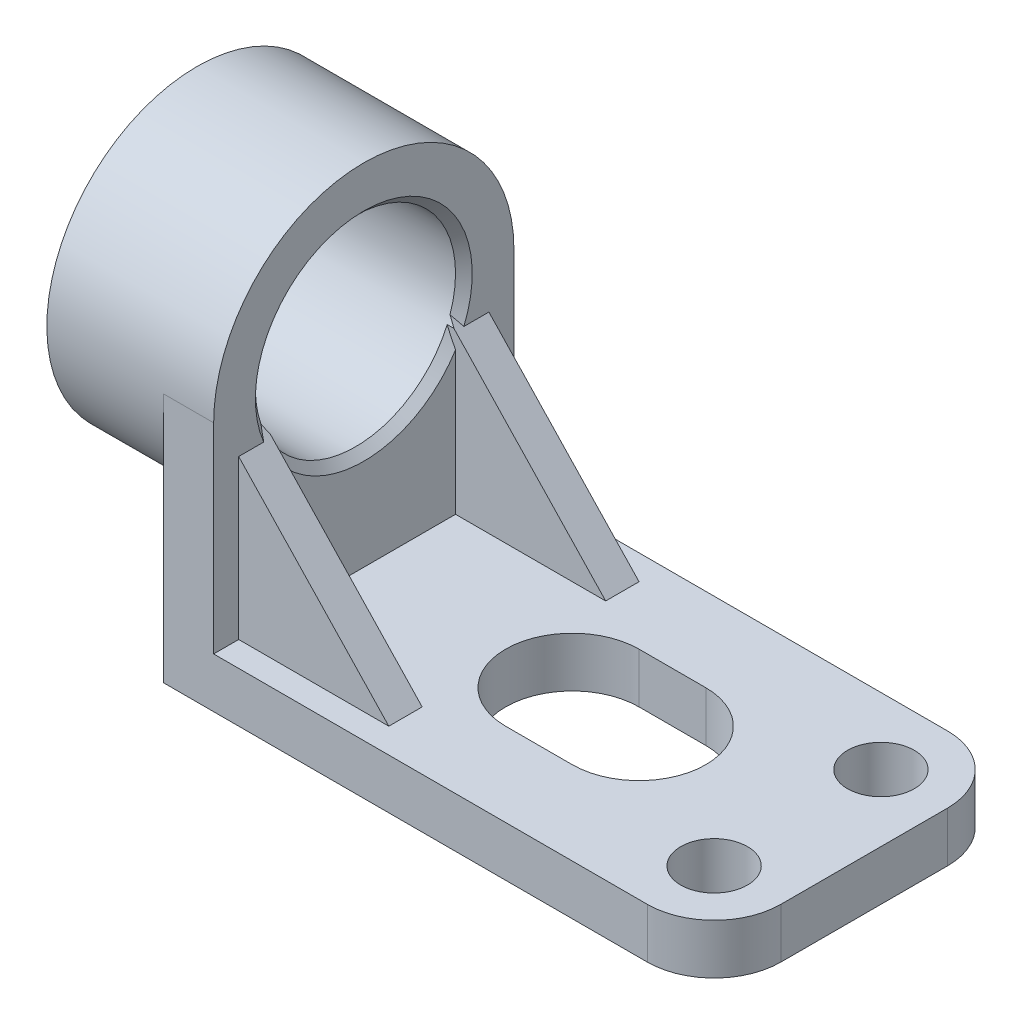
SolidWorks part; units mm, degrees
ref_plane "Front Plane" through (0, 0, 0) normal (0, 0, 1) x (1, 0, 0)
ref_plane "Top Plane" through (0, 0, 0) normal (0, 1, 0) x (1, 0, 0)
ref_plane "Right Plane" through (0, 0, 0) normal (1, 0, 0) x (0, 0, -1)
sketch "Sketch1" plane through (0, 0, 0) normal (0, 0, 1) x (1, 0, 0)
  line L0 (0, 30) -> (0, 0)
  line L1 (0, 0) -> (66, 0)
  line L2 (66, 0) -> (66, 6)
  line L3 (66, 6) -> (6, 6)
  line L4 (6, 6) -> (6, 30)
  line L5 (6, 30) -> (0, 30)
  dimension "D1" = 66
  dimension "D2" = 6
  dimension "D3" = 30
  dimension "D4" = 6
extrude "Boss-Extrude1" add sketch "Sketch1" along normal blind 36
sketch "Sketch2" plane through (6, 0, 0) normal (1, 0, 0) x (0, 0, -1)
  line L0 (-36, 30) -> (0, 30) construction
  line L1 (0, 6) -> (0, 30) construction
  circle A0 centre (-18, 30) radius 18
extrude "Boss-Extrude2" add sketch "Sketch2" against normal blind 20
sketch "Sketch3" plane through (0, 0, 0) normal (0, 0, 1) x (1, 0, 0)
  line L0 (6, 25) -> (24, 6)
  line L1 (66, 6) -> (6, 6) construction
  line L2 (24, 6) -> (6, 6)
  line L3 (6, 6) -> (6, 25)
  dimension "D1" = 19
  dimension "D2" = 18
extrude "Boss-Extrude3" add sketch "Sketch3" along normal blind 4 from offset 3
ref_plane "Plane1" through (0, 0, 18) normal (0, 0, 1) x (1, 0, 0)
mirror "Mirror1" about plane through (0, 0, 18) normal (0, 0, 1) of "Boss-Extrude3"
hole_wizard "Hole1" positions "Sketch6" profile "Sketch5" legacy end condition up to next
sketch "Sketch6" plane through (-14, 0, 0) normal (-1, 0, 0) x (0, 0, 1)
  point P0 (18, 30)
sketch "Sketch5" plane through (-14, 30, 18) normal (0, 1, 0) x (0, 0, 1)
  line L0 (0, 0) -> (0, 20)
  line L1 (0, 20) -> (12, 20)
  line L2 (12, 20) -> (12, 0)
  line L3 (12, 0) -> (0, 0)
  line L4 (0, 110) -> (0, -10) construction
  dimension "Diameter" = 24
  dimension "Depth" = 20
chamfer "Chamfer1" distance 1 angle 45 2 edges at (-14, 30, 30) (6, 18, 18)
sketch "Sketch7" plane through (0, 6, 0) normal (0, 1, 0) x (1, 0, 0)
  line L0 (66, -18) -> (10.5038, -18) construction
  line L1 (66, -36) -> (66, 0) construction
  line L2 (31, -18) -> (39, -18) construction
  line L3 (31, -10) -> (39, -10)
  line L4 (31, -26) -> (39, -26)
  line L5 (6, -36) -> (6, 0) construction
  arc A0 (31, -10) -> (31, -26) centre (31, -18) ccw
  arc A1 (39, -26) -> (39, -10) centre (39, -18) ccw
  point P6 (35, -18)
  dimension "D2" = 8
  dimension "D1" = 8
  dimension "D3" = 29
extrude "Cut-Extrude1" cut sketch "Sketch7" against normal through all
fillet "Fillet1" radius 8 2 edges at (66, 3, 0) (66, 3, 36)
hole_wizard "Hole2" positions "Sketch8" profile "Sketch9" legacy end condition up to next
sketch "Sketch8" plane through (0, 6, 0) normal (0, 1, 0) x (1, 0, 0)
  point P0 (58, -8)
  point P3 (58, -28)
sketch "Sketch9" plane through (58, 6, 8) normal (1, 0, 0) x (0, 0, 1)
  line L0 (0, 0) -> (0, 6)
  line L1 (0, 6) -> (4, 6)
  line L2 (4, 6) -> (4, 0)
  line L3 (4, 0) -> (0, 0)
  line L4 (0, 110) -> (0, -10) construction
  dimension "Diameter" = 8
  dimension "Depth" = 6
